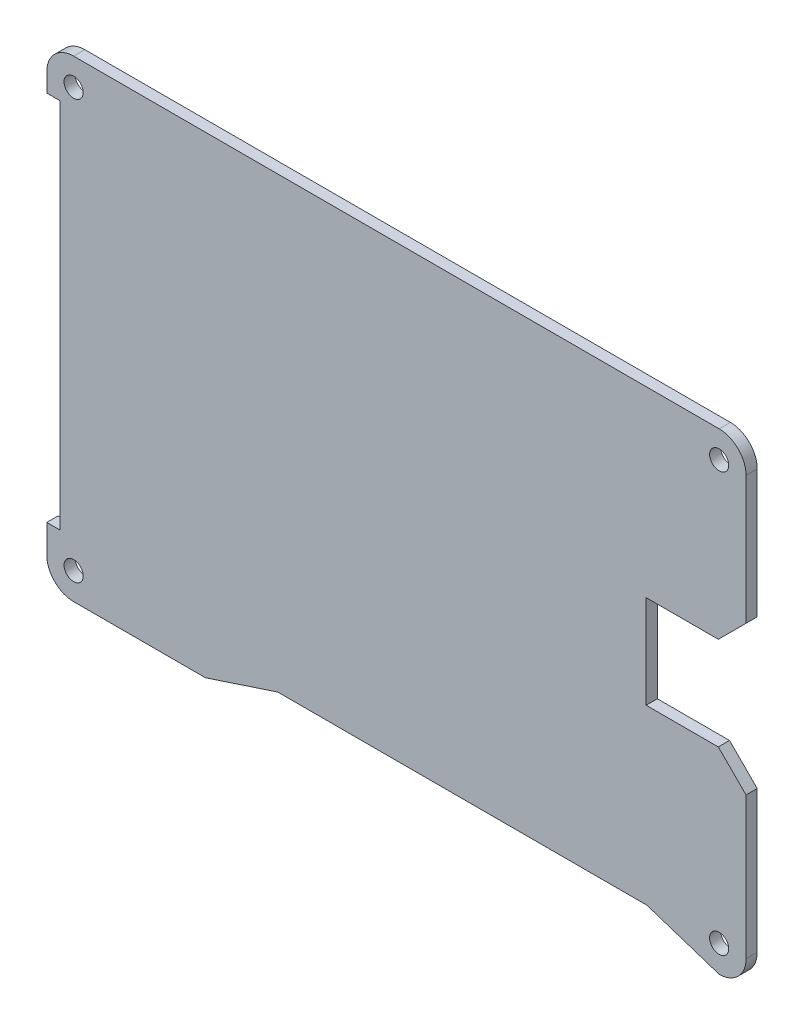
SolidWorks part; units mm, degrees
ref_plane "Front Plane" through (0, 0, 0) normal (0, 0, 1) x (1, 0, 0)
ref_plane "Top Plane" through (0, 0, 0) normal (0, 1, 0) x (1, 0, 0)
ref_plane "Right Plane" through (0, 0, 0) normal (1, 0, 0) x (0, 0, -1)
sketch "Sketch1" plane through (0, 0, 0) normal (0, 0, 1) x (1, 0, 0)
  line L0 (-301.9473, 111.7465) -> (-305.8779, 115.6771) construction
  line L1 (-305.8779, 115.6771) -> (-316.1078, 115.6771) construction
  line L2 (-316.1078, 115.6771) -> (-316.1078, 128.8851) construction
  line L3 (-316.1078, 128.8851) -> (-305.8779, 128.8851) construction
  line L4 (-305.8779, 128.8851) -> (-301.9473, 132.8157) construction
  line L5 (-301.9473, 132.8157) -> (-301.9473, 150.9704) construction
  line L6 (-305.7573, 154.7804) -> (-397.2471, 154.7804) construction
  line L7 (-401.0571, 150.9566) -> (-401.0571, 148.341) construction
  line L8 (-401.0571, 148.341) -> (-399.1521, 148.341) construction
  line L9 (-399.1521, 148.341) -> (-399.1521, 95.6449) construction
  line L10 (-399.1521, 95.6449) -> (-401.0571, 95.6449) construction
  line L11 (-401.0571, 95.6449) -> (-401.0571, 91.6593) construction
  line L12 (-397.2472, 87.8217) -> (-378.5565, 87.8217) construction
  line L13 (-378.5565, 87.8217) -> (-368.3165, 91.1883) construction
  line L14 (-368.3165, 91.1883) -> (-315.9973, 91.1883) construction
  line L15 (-315.9973, 91.1883) -> (-305.7573, 87.8217) construction
  line L16 (-301.9473, 91.6317) -> (-301.9473, 111.7465) construction
  line L17 (-301.9473, 111.7465) -> (-305.8779, 115.6771)
  line L18 (-305.8779, 115.6771) -> (-316.1078, 115.6771)
  line L19 (-316.1078, 115.6771) -> (-316.1078, 128.8851)
  line L20 (-316.1078, 128.8851) -> (-305.8779, 128.8851)
  line L21 (-305.8779, 128.8851) -> (-301.9473, 132.8157)
  line L22 (-301.9473, 132.8157) -> (-301.9473, 150.9704)
  line L23 (-305.7573, 154.7804) -> (-397.2471, 154.7804)
  line L24 (-401.0571, 150.9566) -> (-401.0571, 148.341)
  line L25 (-401.0571, 148.341) -> (-399.1521, 148.341)
  line L26 (-399.1521, 148.341) -> (-399.1521, 95.6449)
  line L27 (-399.1521, 95.6449) -> (-401.0571, 95.6449)
  line L28 (-401.0571, 95.6449) -> (-401.0571, 91.6593)
  line L29 (-397.2472, 87.8217) -> (-378.5565, 87.8217)
  line L30 (-378.5565, 87.8217) -> (-368.3165, 91.1883)
  line L31 (-368.3165, 91.1883) -> (-315.9973, 91.1883)
  line L32 (-315.9973, 91.1883) -> (-305.7573, 87.8217)
  line L33 (-301.9473, 91.6317) -> (-301.9473, 111.7465)
  circle A0 centre (-305.7573, 91.6317) radius 1.3559 construction
  circle A1 centre (-305.7573, 150.9704) radius 1.3559 construction
  circle A2 centre (-397.2471, 150.9704) radius 1.3559 construction
  circle A3 centre (-397.2472, 91.6317) radius 1.3559 construction
  circle A4 centre (-305.7573, 91.6317) radius 1.3559
  circle A5 centre (-305.7573, 150.9704) radius 1.3559
  circle A6 centre (-397.2471, 150.9704) radius 1.3559
  circle A7 centre (-397.2472, 91.6317) radius 1.3559
  arc A8 (-301.9473, 150.9704) -> (-305.7573, 154.7804) centre (-305.7573, 150.9704) ccw construction
  arc A9 (-397.2471, 154.7804) -> (-401.0571, 150.9566) centre (-397.2471, 150.9704) ccw construction
  arc A10 (-401.0571, 91.6593) -> (-397.2472, 87.8217) centre (-397.2472, 91.6317) ccw construction
  arc A11 (-305.7573, 87.8217) -> (-301.9473, 91.6317) centre (-305.7573, 91.6317) ccw construction
  arc A12 (-301.9473, 150.9704) -> (-305.7573, 154.7804) centre (-305.7573, 150.9704) ccw
  arc A13 (-397.2471, 154.7804) -> (-401.0571, 150.9566) centre (-397.2471, 150.9704) ccw
  arc A14 (-401.0571, 91.6593) -> (-397.2472, 87.8217) centre (-397.2472, 91.6317) ccw
  arc A15 (-305.7573, 87.8217) -> (-301.9473, 91.6317) centre (-305.7573, 91.6317) ccw
extrude "Boss-Extrude1" add sketch "Sketch1" along normal blind 1.5875
